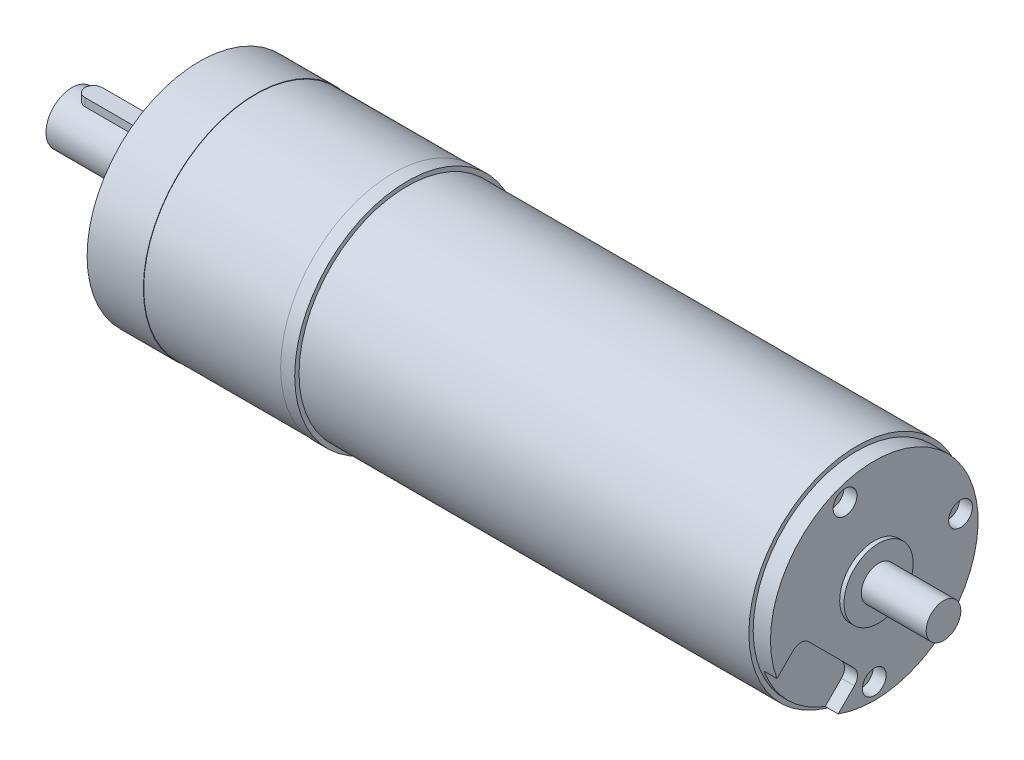
SolidWorks part; units mm, degrees
ref_plane "Front Plane" through (0, 0, 0) normal (0, 0, 1) x (1, 0, 0)
ref_plane "Top Plane" through (0, 0, 0) normal (0, 1, 0) x (1, 0, 0)
ref_plane "Right Plane" through (0, 0, 0) normal (1, 0, 0) x (0, 0, -1)
sketch "Sketch1" plane through (0, 0, 0) normal (0, 1, 0) x (1, 0, 0)
  line L0 (-131.194, 0) -> (137.8562, 0) construction
sketch "Sketch2" plane through (0, 0, 0) normal (0, 1, 0) x (1, 0, 0)
  line L0 (-77.5, 0) -> (-77.5, 6)
  line L1 (-200131.194, 0) -> (200137.8562, 0) construction
  line L2 (-77.5, 6) -> (-51.5, 6)
  line L3 (-51.5, 6) -> (-51.5, 16)
  line L4 (-51.5, 16) -> (-48, 16)
  line L5 (-48, 16) -> (-48, 26)
  line L6 (-48, 26) -> (-35, 26)
  line L7 (-35, 26) -> (-35, 25.9)
  line L8 (-35, 25.9) -> (-3.25, 25.9)
  line L9 (-3.25, 25.9) -> (-3.25, 26)
  line L10 (-3.25, 26) -> (0, 26)
  line L11 (0, 26) -> (0, 25)
  line L12 (0, 25) -> (104, 25)
  line L13 (104, 25) -> (104, 24)
  line L14 (104, 24) -> (108, 24)
  line L15 (108, 24) -> (108, 8)
  line L16 (108, 8) -> (109, 8)
  line L17 (109, 8) -> (109, 4)
  line L18 (109, 4) -> (124, 4)
  line L19 (124, 4) -> (124, 0)
  line L20 (124, 0) -> (-77.5, 0)
  line L21 (0, 25) -> (0, 0) construction
  dimension "D1" = 6
  dimension "D2" = 16
  dimension "D3" = 26
  dimension "D4" = 25.9
  dimension "D5" = 26
  dimension "D6" = 25
  dimension "D7" = 24
  dimension "D8" = 8
  dimension "D9" = 4
  dimension "D10" = 26
  dimension "D11" = 13
  dimension "D12" = 48
  dimension "D13" = 3.25
  dimension "D14" = 1
  dimension "D15" = 15
  dimension "D16" = 4
  dimension "D17" = 156
  dimension "D18" = 3.5
revolve "Revolve1" add sketch "Sketch2" angle 360 about L0
ref_plane "Plane1" through (0, 6, 0) normal (0, 1, 0) x (1, 0, 0)
sketch "Sketch3" plane through (0, 6, 0) normal (0, 1, 0) x (1, 0, 0)
  line L0 (-77.5, 0) -> (-74.5, 0) construction
  line L1 (-77.5, 6) -> (-77.5, -6) construction
  line L2 (-74.5, 0) -> (-72.5, 0) construction
  line L3 (-72.5, 0) -> (-56.5, 0) construction
  line L4 (-56.5, 0) -> (-54.5, 0) construction
  line L5 (-54.5, 0) -> (-51.5, 0) construction
  line L6 (-51.5, 6) -> (-51.5, -6) construction
  line L7 (-72.5, 2) -> (-56.5, 2)
  line L8 (-56.5, -2) -> (-72.5, -2)
  circle A0 centre (-72.5, 0) radius 2
  circle A1 centre (-56.5, 0) radius 2
  dimension "D1" = 4
  dimension "D2" = 20
extrude "Boss-Extrude1" add sketch "Sketch3" along normal blind 1.5 and the other way blind 1.5 contours A1 L7 A0 L8 | A0 | A1 region at (-64.5, 6, 0) region at (-72.5, 6, 0) region at (-56.5, 6, 0)
sketch "Sketch4" plane through (-77.5, 0, 0) normal (-1, 0, 0) x (0, 0, 1)
  circle A0 centre (0, 0) radius 3
  dimension "D1" = 6
extrude "Cut-Extrude1" cut sketch "Sketch4" against normal blind 3.5
hole_wizard "Tap Drill for M4x0.7 Tap1" positions "Sketch6" profile "Sketch7" hole size "M4x0.7" standard "ANSI Metric"
sketch "Sketch6" plane through (-74, 0, 0) normal (-1, 0, 0) x (0, 0, 1)
  point P0 (0, 0)
sketch "Sketch7" plane through (-74, 0, 0) normal (0, 1, 0) x (0, 0, 1)
  line L0 (0, 0) -> (0, 10.9914)
  line L1 (0, 10.9914) -> (1.65, 10)
  line L2 (1.65, 10) -> (1.65, 0)
  line L5 (1.65, 0) -> (0, 0)
  line L10 (0, 10.9914) -> (-1.65, 10) construction
  line L11 (0, -6.35) -> (0, 107.95) construction
  dimension "Hole Dia." = 3.3
  dimension "Hole Depth" = 10
  dimension "Drill Angle" = 118
sketch "Sketch8" plane through (-48, 0, 0) normal (-1, 0, 0) x (0, 0, 1)
  line L0 (0, 0) -> (0, 16) construction
  line L1 (0, 16) -> (0, 20) construction
  line L2 (0, 20) -> (0, 22.5) construction
  line L3 (0, 22.5) -> (0, 25) construction
  line L4 (0, 25) -> (0, 26) construction
  line L5 (0, 0) -> (11.3137, 11.3137) construction
  line L6 (11.3137, 11.3137) -> (12.3744, 12.3744) construction
  line L7 (12.3744, 12.3744) -> (14.1421, 14.1421) construction
  line L8 (14.1421, 14.1421) -> (15.9099, 15.9099) construction
  line L9 (15.9099, 15.9099) -> (18.3848, 18.3848) construction
  circle A0 centre (0, 0) radius 16 construction
  circle A1 centre (0, 22.5) radius 2.5
  circle A2 centre (0, 0) radius 26 construction
  circle A3 centre (0, 0) radius 16 construction
  circle A4 centre (14.1421, 14.1421) radius 2.5
  circle A5 centre (22.5, 0) radius 2.5
  circle A6 centre (14.1421, -14.1421) radius 2.5
  circle A7 centre (0, -22.5) radius 2.5
  circle A8 centre (-14.1421, -14.1421) radius 2.5
  circle A9 centre (-22.5, 0) radius 2.5
  circle A10 centre (-14.1421, 14.1421) radius 2.5
  point P21 (0, 22.1979)
  point P36 (0, 0)
  dimension "D1" = 5
  dimension "D4" = 5
  dimension "D2" = 3.5
  dimension "D3" = 45
  dimension "D5" = 6
  dimension "D6" = 4
hole_wizard "Tap Drill for M5x0.8 Tap1" positions "Sketch9" profile "Sketch10" hole size "M5x0.8" standard "ANSI Metric"
sketch "Sketch9" plane through (-48, 0, 0) normal (-1, 0, 0) x (0, 0, 1)
  point P0 (0, 22.5)
  point P3 (14.1421, 14.1421)
  point P6 (22.5, 0)
  point P9 (14.1421, -14.1421)
  point P12 (0, -22.5)
  point P15 (-14.1421, -14.1421)
  point P18 (-22.5, 0)
  point P21 (-14.1421, 14.1421)
sketch "Sketch10" plane through (-48, 22.5, 0) normal (0, 1, 0) x (0, 0, 1)
  line L0 (0, 0) -> (0, 11.2618)
  line L1 (0, 11.2618) -> (2.1, 10)
  line L2 (2.1, 10) -> (2.1, 0)
  line L5 (2.1, 0) -> (0, 0)
  line L10 (0, 11.2618) -> (-2.1, 10) construction
  line L11 (0, -6.35) -> (0, 107.95) construction
  dimension "Hole Dia." = 4.2
  dimension "Hole Depth" = 10
  dimension "Drill Angle" = 118
sketch "Sketch12" plane through (108, 0, 0) normal (1, 0, 0) x (0, 0, -1)
  line L0 (0, 0) -> (-5.8416, 16.4962) construction
  line L1 (-5.8416, 16.4962) -> (-6.7596, 19.0885) construction
  line L2 (-6.7596, 19.0885) -> (-7.6776, 21.6808) construction
  line L3 (-7.6776, 21.6808) -> (-8.679, 24.5087) construction
  line L4 (0, 0) -> (0, 26) construction
  line L5 (0, 0) -> (19.9575, 3.4293) construction
  line L6 (0, 0) -> (0, -20.25) construction
  circle A0 centre (-6.7596, 19.0885) radius 2.75
  circle A1 centre (19.9575, 3.4293) radius 2.75
  circle A2 centre (0, 0) radius 26 construction
  circle A3 centre (0, -20.25) radius 2.75
  circle A4 centre (0, 0) radius 20.25 construction
  dimension "D1" = 5.5
  dimension "D2" = 19.5
  dimension "D3" = 20.25
  dimension "D5" = 99.75
  dimension "D4" = 80.25
sketch "Sketch13" plane through (108, 0, 0) normal (1, 0, 0) x (0, 0, -1)
  line L0 (-16.9706, -2.8284) -> (-25.4558, -11.3137)
  line L2 (-25.4558, -11.3137) -> (-11.3137, -25.4558)
  line L3 (-11.3137, -25.4558) -> (-2.8284, -16.9706)
  line L4 (-2.8284, -16.9706) -> (-16.9706, -2.8284)
  line L5 (0, 0) -> (-9.8995, -9.8995) construction
  line L6 (0, 0) -> (0, -26) construction
  circle A0 centre (0, 0) radius 26 construction
  dimension "D1" = 12
  dimension "D2" = 20
  dimension "D3" = 45
extrude "Cut-Extrude2" cut sketch "Sketch13" against normal blind 3
fillet "Fillet1" radius 2.5 2 edges at (106.5, -16.9706, 2.8284) (106.5, -2.8284, 16.9706)
extrude "Cut-Extrude3" cut sketch "Sketch12" against normal blind 3
hole_wizard "Tap Drill for M3x0.5 Tap2" positions "Sketch16" profile "Sketch17" hole size "M3x0.5" standard "ANSI Metric"
sketch "Sketch16" plane through (105, 0, 0) normal (1, 0, 0) x (0, 0, -1)
  point P0 (-6.7596, 19.0885)
  point P3 (19.9575, 3.4293)
  point P6 (0, -20.25)
sketch "Sketch17" plane through (105, 19.0885, 6.7596) normal (0, 1, 0) x (0, 0, -1)
  line L0 (0, 0) -> (0, 10.7511)
  line L1 (0, 10.7511) -> (1.25, 10)
  line L2 (1.25, 10) -> (1.25, 0)
  line L5 (1.25, 0) -> (0, 0)
  line L10 (0, 10.7511) -> (-1.25, 10) construction
  line L11 (0, -6.35) -> (0, 107.95) construction
  dimension "Hole Dia." = 2.5
  dimension "Hole Depth" = 10
  dimension "Drill Angle" = 118
